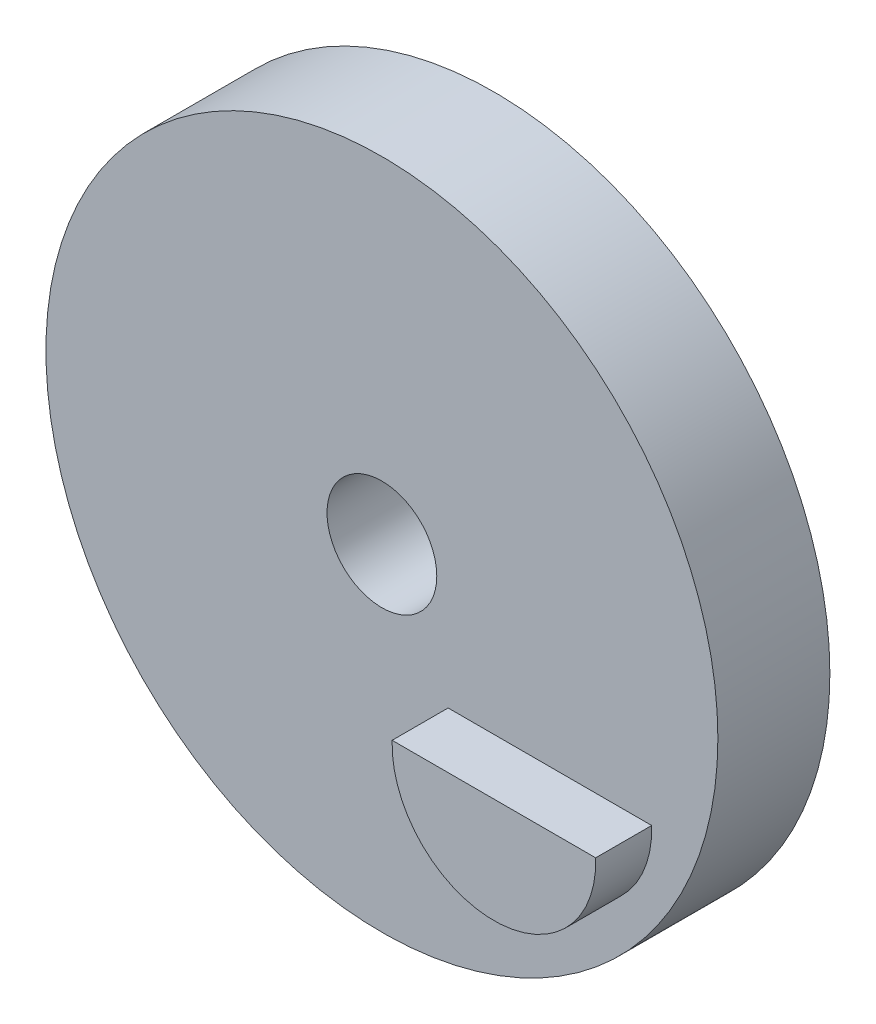
SolidWorks part; units mm, degrees
ref_plane "Front Plane" through (0, 0, 0) normal (0, 0, 1) x (1, 0, 0)
ref_plane "Top Plane" through (0, 0, 0) normal (0, 1, 0) x (1, 0, 0)
ref_plane "Right Plane" through (0, 0, 0) normal (1, 0, 0) x (0, 0, -1)
sketch "Sketch1" plane through (0, 0, 0) normal (0, 0, 1) x (1, 0, 0)
  line L0 (-169.7289, -38.1) -> (169.7289, -38.1) construction
  line L1 (-110.0162, 38.1) -> (110.0162, 38.1) construction
  circle A0 centre (0, 0) radius 38.1
  circle A1 centre (0, 0) radius 6.223
  point P7 (0, -38.1)
  point P14 (0, 38.1)
  dimension "D1" = 76.2
  dimension "D3" = 12.446
extrude "Boss-Extrude1" add sketch "Sketch1" along normal blind 12.7
sketch "Sketch2" plane through (0, 0, 0) normal (0, 0, 1) x (1, 0, 0)
  line L0 (7.5097, -12.3083) -> (30.5903, -12.3083)
  arc A2 (7.5097, -12.3083) -> (30.5903, -12.3083) centre (19.05, -12.7) ccw
  point P4 (0, 0)
  point P7 (19.7348, -10.8646)
  dimension "D1" = 19.05
  dimension "D2" = 12.7
extrude "Boss-Extrude2" add sketch "Sketch2" along normal blind 19.05
